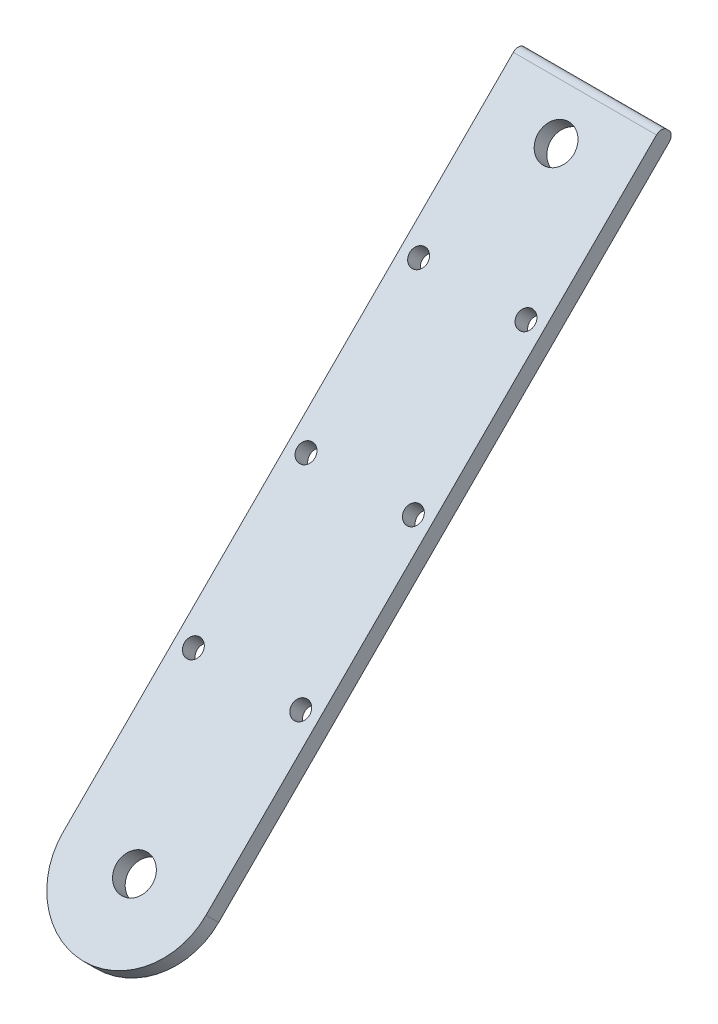
SolidWorks part; units mm, degrees
ref_plane "Front Plane" through (0, 0, 0) normal (0, 0, 1) x (1, 0, 0)
ref_plane "Top Plane" through (0, 0, 0) normal (0, 1, 0) x (1, 0, 0)
ref_plane "Right Plane" through (0, 0, 0) normal (1, 0, 0) x (0, 0, -1)
sketch "Sketch1" plane through (0, 0, 0) normal (1, 0, 0) x (0, 0, -1)
  line L2 (-77.2861, 2.727) -> (-76.9594, 2.4004)
  line L4 (-57.1843, -14.5463) -> (-34.2536, 8.3843)
  line L6 (-37.7868, 11.9175) -> (-60.7175, -11.0131)
  line L7 (-60.7175, -13.8415) -> (-60.0127, -14.5463)
  line L8 (-60.7175, -11.0131) -> (-62.1317, -12.4273)
  line L11 (-57.1843, -14.5463) -> (81.4087, 124.0466)
  line L12 (-60.7175, -11.0131) -> (77.8754, 127.5798)
  line L13 (81.4087, 126.875) -> (80.7039, 127.5798)
  line L14 (-73.65, 1.5554) -> (-74.4574, 1.5554)
  line L16 (-76.9405, 2.4193) -> (-76.9594, 2.4004)
  line L17 (-57.1843, -14.5463) -> (-58.5985, -15.9606)
  line L19 (-60.7175, -13.8415) -> (-62.1317, -12.4273)
  line L20 (-60.0127, -14.5463) -> (-58.5985, -15.9606)
  arc A2 (-74.4574, 1.5554) -> (-77.2861, 2.727) centre (-74.4574, 5.5557) cw
  arc A4 (80.7039, 127.5798) -> (77.8754, 127.5798) centre (79.2897, 126.1656) ccw
  arc A5 (81.4087, 126.875) -> (81.4087, 124.0466) centre (79.9945, 125.4608) cw
  point P10 (82.8229, 125.4608)
  dimension "D2" = 2
extrude "Boss-Extrude1" add sketch "Sketch1" along normal blind 40 contours L7 L4 L11 A5 L13 A4 L12 L6 region at (0, 56.3956, -10.2245)
fillet "Fillet3" radius 20 1 edges at (40, -14.1939, 60.3651)
fillet "Fillet4" radius 20 1 edges at (0, -14.1939, 60.3651)
sketch "Sketch2" plane through (0, 24.8522, 24.8522) normal (0, 0.7071, 0.7071) x (1, 0, 0)
  circle A0 centre (20, -32.7212) radius 5
  circle A1 centre (35, 100.7788) radius 2.5
  circle A2 centre (35, 56.2788) radius 2.5
  circle A3 centre (35, 11.7788) radius 2.5
  circle A4 centre (5, 11.7788) radius 2.5
  circle A5 centre (5, 56.2788) radius 2.5
  circle A6 centre (5, 100.7788) radius 2.5
extrude "Cut-Extrude1" cut sketch "Sketch2" against normal blind 5
sketch "Sketch3" plane through (0, 21.319, 21.319) normal (0, -0.7071, -0.7071) x (1, 0, 0)
  circle A0 centre (20, -133.8887) radius 5
  point P4 (0, 0)
extrude "Cut-Extrude2" cut sketch "Sketch3" against normal blind 5 contours A0
